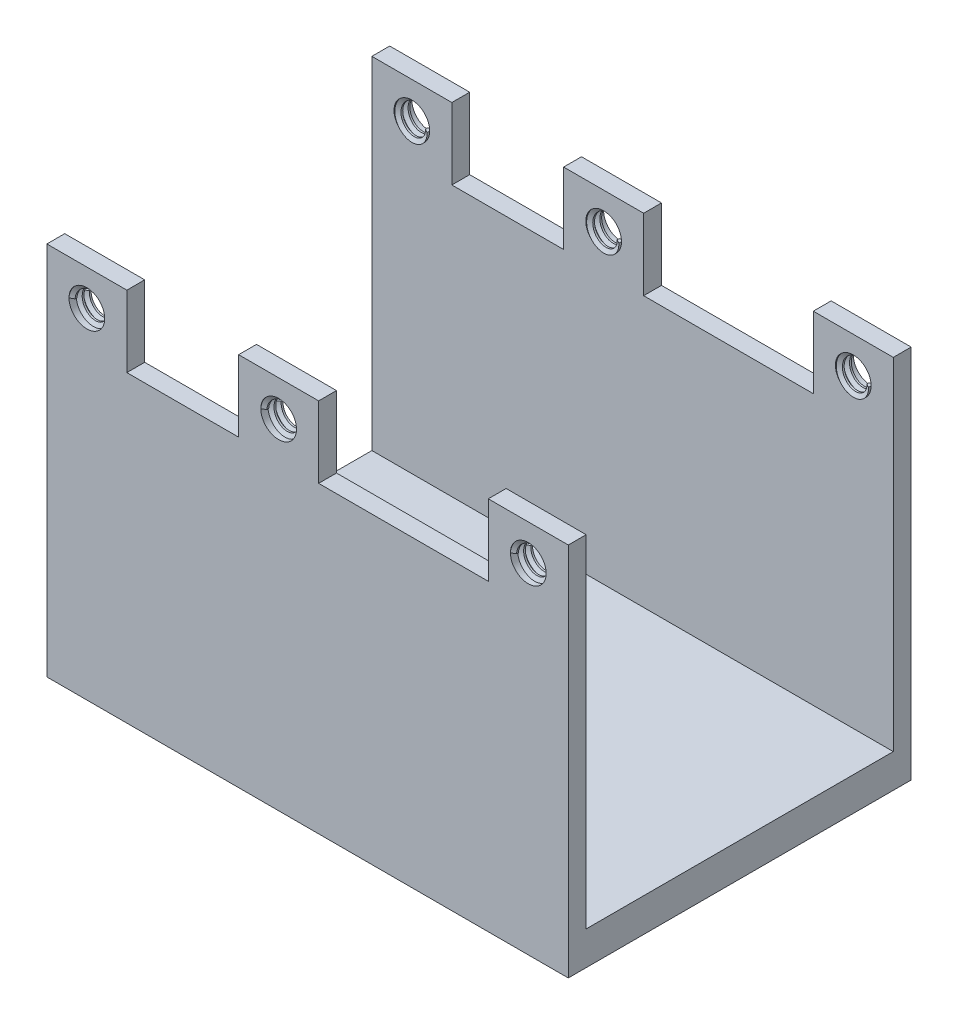
SolidWorks part; units mm, degrees
ref_plane "Front Plane" through (0, 0, 0) normal (0, 0, 1) x (1, 0, 0)
ref_plane "Top Plane" through (0, 0, 0) normal (0, 1, 0) x (1, 0, 0)
ref_plane "Right Plane" through (0, 0, 0) normal (1, 0, 0) x (0, 0, -1)
sketch "Sketch1" plane through (0, 0, 0) normal (0, 0, 1) x (1, 0, 0)
  line L0 (-53.3172, 0) -> (39.3928, 0)
  line L1 (39.3928, 0) -> (39.3928, 66.675)
  line L2 (39.3928, 66.675) -> (25.1688, 66.675)
  line L3 (25.1688, 66.675) -> (25.1688, 53.975)
  line L4 (25.1688, 53.975) -> (-4.9937, 53.975)
  line L5 (-4.9937, 53.975) -> (-4.9937, 66.675)
  line L6 (-4.9937, 66.675) -> (-19.2177, 66.675)
  line L7 (-19.2177, 66.675) -> (-19.2177, 53.975)
  line L8 (-19.2177, 53.975) -> (-39.0932, 53.975)
  line L9 (-39.0932, 53.975) -> (-39.0932, 66.675)
  line L10 (-39.0932, 66.675) -> (-53.3172, 66.675)
  line L11 (-53.3172, 66.675) -> (-53.3172, 0)
  dimension "D1" = 92.71
  dimension "D2" = 14.224
  dimension "D3" = 14.224
  dimension "D4" = 14.224
  dimension "D5" = 30.1625
  dimension "D6" = 66.675
  dimension "D7" = 12.7
  dimension "D8" = 12.7
  dimension "D9" = 12.7
extrude "Boss-Extrude1" add sketch "Sketch1" along normal blind 3.175
sketch "Sketch2" plane through (0, 0, 3.175) normal (0, 0, 1) x (1, 0, 0)
  line L0 (-53.3172, 66.675) -> (-53.3172, 0) construction
  line L1 (-53.3172, 5.969) -> (39.3928, 5.969)
  line L2 (-53.3172, 5.969) -> (-53.3172, 0)
  line L3 (-53.3172, 0) -> (39.3928, 0)
  line L4 (39.3928, 5.969) -> (39.3928, 0)
  dimension "D1" = 5.969
extrude "Boss-Extrude2" add sketch "Sketch2" along normal blind 54.61
ref_plane "Plane1" through (0, 0, 30.48) normal (0, 0, 1) x (1, 0, 0)
mirror "Mirror1" about plane through (0, 0, 30.48) normal (0, 0, 1) of "Boss-Extrude1"
sketch "Sketch3" plane through (0, 0, 60.96) normal (0, 0, 1) x (1, 0, 0)
  line L0 (-39.0932, 60.325) -> (42.6682, 60.325) construction
  line L1 (-39.0932, 53.975) -> (-39.0932, 66.675) construction
  line L2 (-46.2052, 66.675) -> (-46.2052, 20.7462) construction
  line L3 (-39.0932, 66.675) -> (-53.3172, 66.675) construction
  line L4 (-12.1057, 66.675) -> (-12.1057, 24.1212) construction
  line L5 (-4.9937, 66.675) -> (-19.2177, 66.675) construction
  line L6 (32.2808, 66.675) -> (32.2808, 24.7581) construction
  line L7 (39.3928, 66.675) -> (25.1688, 66.675) construction
  line L8 (-39.0932, 60.325) -> (-53.3172, 60.325) construction
  line L9 (-53.3172, 66.675) -> (-53.3172, 0) construction
  circle A0 centre (-46.2052, 60.325) radius 3.175
  circle A1 centre (-12.1057, 60.325) radius 3.175
  circle A2 centre (32.2808, 60.325) radius 3.175
  dimension "D1" = 6.35
  dimension "D2" = 6.35
  dimension "D3" = 6.35
extrude "Cut-Extrude1" cut sketch "Sketch3" against normal through all
thread "Thread1" pitch 1.27 method extrude profile "Thread Profile1" start angle 0, offset 0, length 0, pitch 1.27, diameter 6.35
ref_plane "Plane2" through (-49.3802, 60.325, 60.96) normal (0, -1, 0) x (-1, 0, 0)
sketch "Thread Profile1" plane through (-49.3802, 60.325, 60.96) normal (0, -1, 0) x (-1, 0, 0)
  line L0 (0, 0) -> (0, 1.27) construction
  line L11 (0, 0) -> (0, 1.1112)
  line L12 (0, 1.1112) -> (-0.6874, 0.7144)
  line L13 (-0.6874, 0.7144) -> (-0.6874, 0.3969)
  line L15 (-0.6874, 0.3969) -> (0, 0)
  line L17 (-0.6874, 0.5556) -> (0, 0.5556) construction
  point P2 (0, 0)
  dimension "Pitch" = 1.27
  dimension "Profile_Angle" = 60
  dimension "Profile_Land" = 0.3175
  dimension "Profile_Height" = 0.6874
thread "Thread2" pitch 1.27 method extrude profile "Thread Profile2" start angle 0, offset 0, length 0, pitch 1.27, diameter 6.35
ref_plane "Plane3" through (-15.2807, 60.325, 60.96) normal (0, -1, 0) x (-1, 0, 0)
sketch "Thread Profile2" plane through (-15.2807, 60.325, 60.96) normal (0, -1, 0) x (-1, 0, 0)
  line L0 (0, 0) -> (0, 1.27) construction
  line L11 (0, 0) -> (0, 1.1112)
  line L12 (0, 1.1112) -> (-0.6874, 0.7144)
  line L13 (-0.6874, 0.7144) -> (-0.6874, 0.3969)
  line L15 (-0.6874, 0.3969) -> (0, 0)
  line L17 (-0.6874, 0.5556) -> (0, 0.5556) construction
  point P2 (0, 0)
  dimension "Pitch" = 1.27
  dimension "Profile_Angle" = 60
  dimension "Profile_Land" = 0.3175
  dimension "Profile_Height" = 0.6874
thread "Thread3" pitch 1.27 method extrude profile "Thread Profile3" start angle 0, offset 0, length 0, pitch 1.27, diameter 6.35
ref_plane "Plane4" through (29.1058, 60.325, 60.96) normal (0, -1, 0) x (-1, 0, 0)
sketch "Thread Profile3" plane through (29.1058, 60.325, 60.96) normal (0, -1, 0) x (-1, 0, 0)
  line L0 (0, 0) -> (0, 1.27) construction
  line L11 (0, 0) -> (0, 1.1112)
  line L12 (0, 1.1112) -> (-0.6874, 0.7144)
  line L13 (-0.6874, 0.7144) -> (-0.6874, 0.3969)
  line L15 (-0.6874, 0.3969) -> (0, 0)
  line L17 (-0.6874, 0.5556) -> (0, 0.5556) construction
  point P2 (0, 0)
  dimension "Pitch" = 1.27
  dimension "Profile_Angle" = 60
  dimension "Profile_Land" = 0.3175
  dimension "Profile_Height" = 0.6874
thread "Thread4" pitch 1.27 method extrude profile "Thread Profile4" start angle 0, offset 0, length 0, pitch 1.27, diameter 6.35
ref_plane "Plane5" through (35.4558, 60.325, 0) normal (0, -1, 0) x (1, 0, 0)
sketch "Thread Profile4" plane through (35.4558, 60.325, 0) normal (0, -1, 0) x (1, 0, 0)
  line L0 (0, 0) -> (0, 1.27) construction
  line L11 (0, 0) -> (0, 1.1112)
  line L12 (0, 1.1112) -> (-0.6874, 0.7144)
  line L13 (-0.6874, 0.7144) -> (-0.6874, 0.3969)
  line L15 (-0.6874, 0.3969) -> (0, 0)
  line L17 (-0.6874, 0.5556) -> (0, 0.5556) construction
  point P2 (0, 0)
  dimension "Pitch" = 1.27
  dimension "Profile_Angle" = 60
  dimension "Profile_Land" = 0.3175
  dimension "Profile_Height" = 0.6874
thread "Thread5" pitch 1.27 method extrude profile "Thread Profile5" start angle 0, offset 0, length 0, pitch 1.27, diameter 6.35
ref_plane "Plane6" through (-8.9307, 60.325, 0) normal (0, -1, 0) x (1, 0, 0)
sketch "Thread Profile5" plane through (-8.9307, 60.325, 0) normal (0, -1, 0) x (1, 0, 0)
  line L0 (0, 0) -> (0, 1.27) construction
  line L11 (0, 0) -> (0, 1.1112)
  line L12 (0, 1.1112) -> (-0.6874, 0.7144)
  line L13 (-0.6874, 0.7144) -> (-0.6874, 0.3969)
  line L15 (-0.6874, 0.3969) -> (0, 0)
  line L17 (-0.6874, 0.5556) -> (0, 0.5556) construction
  point P2 (0, 0)
  dimension "Pitch" = 1.27
  dimension "Profile_Angle" = 60
  dimension "Profile_Land" = 0.3175
  dimension "Profile_Height" = 0.6874
thread "Thread6" pitch 1.27 method extrude profile "Thread Profile6" start angle 0, offset 0, length 0, pitch 1.27, diameter 6.35
ref_plane "Plane7" through (-43.0302, 60.325, 0) normal (0, -1, 0) x (1, 0, 0)
sketch "Thread Profile6" plane through (-43.0302, 60.325, 0) normal (0, -1, 0) x (1, 0, 0)
  line L0 (0, 0) -> (0, 1.27) construction
  line L11 (0, 0) -> (0, 1.1112)
  line L12 (0, 1.1112) -> (-0.6874, 0.7144)
  line L13 (-0.6874, 0.7144) -> (-0.6874, 0.3969)
  line L15 (-0.6874, 0.3969) -> (0, 0)
  line L17 (-0.6874, 0.5556) -> (0, 0.5556) construction
  point P2 (0, 0)
  dimension "Pitch" = 1.27
  dimension "Profile_Angle" = 60
  dimension "Profile_Land" = 0.3175
  dimension "Profile_Height" = 0.6874
